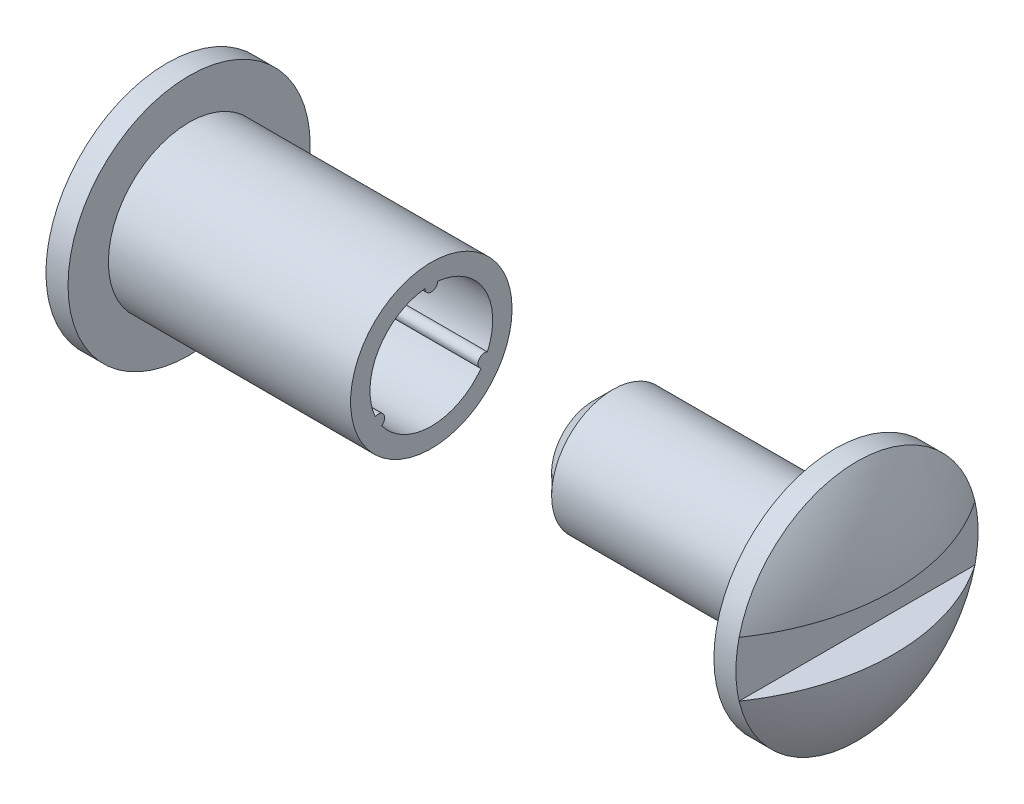
SolidWorks part; units mm, degrees
ref_plane "Front Plane" through (0, 0, 0) normal (0, 0, 1) x (1, 0, 0)
ref_plane "Top Plane" through (0, 0, 0) normal (0, 1, 0) x (1, 0, 0)
ref_plane "Right Plane" through (0, 0, 0) normal (1, 0, 0) x (0, 0, -1)
sketch "Sketch1" plane through (0, 0, 0) normal (0, 0, 1) x (1, 0, 0)
  line L0 (0, 0) -> (9.525, 0) construction
  line L1 (0, 2.413) -> (0, -2.413) construction
  line L2 (9.525, 4.7625) -> (9.525, -4.7625) construction
  line L3 (9.525, 0) -> (11.905, 0) construction
  line L4 (-6.35, 3.175) -> (-6.35, -3.175) construction
  line L5 (-6.35, 0) -> (-15.875, 0) construction
  line L6 (-15.875, 4.7625) -> (-15.875, -4.7625) construction
  line L7 (-6.35, 2.413) -> (-12.7, 2.413) construction
  line L8 (-12.7, 2.413) -> (-12.7, -2.413) construction
  line L9 (-12.7, -2.413) -> (-6.35, -2.413) construction
  line L10 (-15.875, 0) -> (-18.255, 0) construction
  line L11 (9.525, -4.7625) -> (-15.875, -4.7625) construction
  point P18 (-12.7, 0)
  point P19 (-3.175, -4.7625)
  point P21 (2.6458, -2.413)
  dimension "D1" = 6.35
  dimension "D2" = 2.6458
ref_plane "Plane1" through (11.905, 0, 0) normal (1, 0, 0) x (0, 0, -1)
sketch "Sketch2" plane through (0, 0, 0) normal (1, 0, 0) x (0, 0, -1)
  circle A0 centre (0, 0) radius 2.413
extrude "Boss-Extrude1" add sketch "Sketch2" along normal up to vertex (9.525 mm away) up to point (9.525, 0, 0)
sketch "Sketch4" plane through (0, 0, 0) normal (-1, 0, 0) x (0, 0, 1)
  circle A1 centre (0, 0) radius 2.413
  circle A2 centre (0, 0) radius 2.413
  dimension "D1" = 0
chamfer "Chamfer1" distance 0.7937 angle 45 1 edges at (0, 0, -2.413)
curve "Helix/Spiral1" [suppressed] pitch 1.0583 height 10.5833 turns 10 parameters "Pitch"=1.0583
sketch "Sketch5" plane through (0, 0, 0) normal (0, 0, 1) x (1, 0, 0)
  line L0 (0, 2.413) -> (-0.926, 2.413)
  line L1 (0, 2.413) -> (-0.3969, 1.7256)
  line L2 (-0.3969, 1.7256) -> (-0.5292, 1.7256)
  line L3 (-0.5292, 1.7256) -> (-0.926, 2.413)
  line L4 (-0.463, 1.7256) -> (-0.463, 2.413) construction
  line L5 (-0.1984, 2.0693) -> (-0.7276, 2.0693) construction
  dimension "D1" = 0.1323
  dimension "D2" = 0.5292
  dimension "D3" = 60
sweep "Cut-Sweep1" [suppressed] cut profiles "Sketch5" path "Helix/Spiral1"
sketch "Sketch6" plane through (0, 0, 0) normal (0, 0, 1) x (1, 0, 0)
  line L0 (9.525, 0) -> (9.525, 4.7625)
  line L1 (9.525, 4.7625) -> (10.3904, 4.7625)
  line L2 (11.905, 0) -> (11.905, 4.7625) construction
  line L3 (11.905, 0) -> (9.525, 0) construction
  line L5 (9.525, 0) -> (11.905, 0)
  line L6 (11.905, 0) -> (11.905, -1.9812) construction
  arc A0 (11.905, 0) -> (10.3904, 4.7625) centre (3.6598, 0) ccw
  point P10 (11.905, -1.9812)
  dimension "D1" = 0.8654
revolve "Revolve1" add sketch "Sketch6" angle 360 about L3
ref_plane "Plane2" through (-3.175, 0, 0) normal (1, 0, 0) x (0, 0, -1)
sketch "Sketch17" plane through (11.905, 0, 0) normal (1, 0, 0) x (0, 0, -1)
  line L0 (-4.7625, 0) -> (4.7625, 0) construction
  line L1 (-4.7625, 1.0858) -> (4.7625, 1.0858)
  line L2 (-4.7625, 1.0858) -> (-4.7625, -1.0858)
  line L3 (-4.7625, -1.0858) -> (4.7625, -1.0858)
  line L4 (4.7625, 1.0858) -> (4.7625, -1.0858)
  circle A0 centre (0, 0) radius 4.7625 construction
  dimension "D1" = 2.1717
extrude "Cut-Extrude5" cut sketch "Sketch17" against normal up to vertex (1.5145 mm away) up to point (10.3904, 4.7625, 0)
mirror "Mirror1" about plane through (-3.175, 0, 0) normal (1, 0, 0) of bodies 118 107 106
ref_plane "Plane3" through (-6.35, 0, 0) normal (1, 0, 0) x (0, 0, -1)
sketch "Sketch11" plane through (-6.35, 0, 0) normal (1, 0, 0) x (0, 0, -1)
  line L0 (0, 2.413) -> (0, 0) construction
  line L1 (0, 0) -> (-2.0897, -1.2065) construction
  line L2 (0, 0) -> (2.0897, -1.2065) construction
  circle A0 centre (0, 0) radius 3.175
  arc A1 (-0.2536, 2.3996) -> (-2.205, -0.9802) centre (0, 0) ccw
  arc A2 (-1.9513, -1.4195) -> (-2.205, -0.9802) centre (-2.0897, -1.2065) ccw
  arc A3 (-0.2536, 2.3996) -> (0.2536, 2.3996) centre (0, 2.413) ccw
  arc A4 (2.205, -0.9802) -> (1.9513, -1.4195) centre (2.0897, -1.2065) ccw
  arc A5 (2.205, -0.9802) -> (0.2536, 2.3996) centre (0, 0) ccw
  arc A6 (-1.9513, -1.4195) -> (1.9513, -1.4195) centre (0, 0) ccw
  dimension "D3" = 0.508
  dimension "D1" = 120
  dimension "D2" = 120
extrude "Boss-Extrude3" add sketch "Sketch11" against normal up to surface (9.525 mm away) separate body
combine bodies "Combine1" operation type add bodies to combine 111 110
combine bodies "Combine2" operation type add bodies to combine 118 101
equation "\"D1@Sketch5\" = \"Pitch@Helix/Spiral1\"*.125"
equation "\"D2@Sketch5\" = \"Pitch@Helix/Spiral1\"*.50"
equation "\"D3@Helix/Spiral1\" = \"Screw Length@Sketch1\"+\"Pitch@Helix/Spiral1\""
equation "\"D1@Chamfer1\" = \"Pitch@Helix/Spiral1\"*.750"
equation "\"D1@Sketch6\" = \"Head Height@Sketch1\"/2.75"
equation "\"D2@Sketch1\" = \"Pitch@Helix/Spiral1\"*2.50"
equation "\"D1@Sketch17\" = \"Screw Dia@Sketch1\"*.45"
